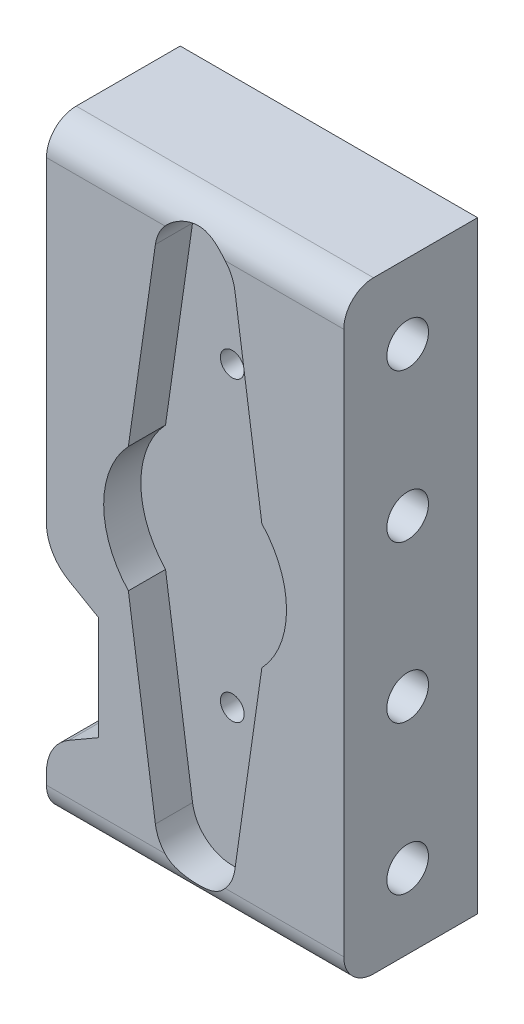
SolidWorks part; units mm, degrees
material "PLA_Holder_Servo"
ref_plane "Front Plane" through (0, 0, 0) normal (0, 0, 1) x (1, 0, 0)
ref_plane "Top Plane" through (0, 0, 0) normal (0, 1, 0) x (1, 0, 0)
ref_plane "Right Plane" through (0, 0, 0) normal (1, 0, 0) x (0, 0, -1)
sketch "Sketch1" plane through (0, 0, 0) normal (0, 0, 1) x (1, 0, 0)
  line L0 (-10, 20.2804) -> (-10, -20.2804)
  line L1 (-10, -20.2804) -> (10, -20.2804)
  line L2 (10, -20.2804) -> (10, 20.2804)
  line L3 (10, 20.2804) -> (-10, 20.2804)
  line L4 (10, -20.2804) -> (-10, 20.2804) construction
  line L5 (10, 20.2804) -> (-10, -20.2804) construction
  point P4 (0, 0)
  dimension "D1" = 20
  dimension "D2" = 40.5608
extrude "Boss-Extrude1" add sketch "Sketch1" against normal blind 9
sketch "Sketch6" plane through (10, 0, 0) normal (1, 0, 0) x (0, 0, -1)
  line L0 (0, -20.2804) -> (0, 20.2804) construction
  line L2 (4.3, 4.95) -> (4.3, 15.6283) construction
  line L3 (0, 0) -> (9, 0) construction
  line L4 (9, -20.2804) -> (9, 20.2804) construction
  line L5 (4.3, -15.2652) -> (4.3, -5.2652) construction
  line L6 (-4.0611, -10.2652) -> (12.6611, -10.2652) construction
  line L7 (9, -20.2804) -> (0, -20.2804) construction
  line L8 (-4.0611, -0.25) -> (12.6611, -0.25) construction
  circle A0 centre (4.3, -15.2652) radius 1.4
  circle A1 centre (4.3, -5.2652) radius 1.4
  circle A2 centre (4.3, 15.2652) radius 1.4
  circle A3 centre (4.3, 5.2652) radius 1.4
  point P18 (4.3, -10.2652)
  point P22 (4.3, -10.2652)
  dimension "D1" = 2.8
  dimension "D2" = 4.7
  dimension "D3" = 10.0152
  dimension "D4" = 10
  dimension "D5" = 10.0152
extrude "Cut-Extrude1" cut sketch "Sketch6" against normal blind 10
sketch "Sketch8" plane through (0, 0, 0) normal (0, 0, 1) x (1, 0, 0)
  line L0 (-10, 20.2804) -> (10, -20.2804) construction
  line L1 (-4.489, -4.2038) -> (-2.6727, -16.8829)
  line L2 (4.3, 4.1125) -> (4.3, -4.1125) construction
  line L3 (0, -16.5) -> (0, 16.5) construction
  line L4 (2.6727, -16.8829) -> (4.489, -4.2038)
  line L5 (-4.3, 4.1125) -> (4.3, 4.1125) construction
  line L6 (-4.3, -4.1125) -> (4.3, -4.1125) construction
  line L7 (4.489, 4.2038) -> (2.6727, 16.8829)
  line L8 (-2.6727, 16.8829) -> (-4.489, 4.2038)
  line L12 (-4.3, -4.1125) -> (-2.4747, -16.8545) construction
  line L13 (2.4747, -16.8545) -> (4.3, -4.1125) construction
  line L14 (4.3, 4.1125) -> (2.4747, 16.8545) construction
  line L15 (-2.4747, 16.8545) -> (-4.3, 4.1125) construction
  arc A0 (-2.6727, -16.8829) -> (2.6727, -16.8829) centre (0, -16.5) ccw
  arc A1 (4.489, -4.2038) -> (4.489, 4.2038) centre (0, 0) ccw
  arc A2 (2.6727, 16.8829) -> (-2.6727, 16.8829) centre (0, 16.5) ccw
  arc A3 (-4.489, 4.2038) -> (-4.489, -4.2038) centre (0, 0) ccw
  arc A12 (-4.3, 4.1125) -> (-4.3, -4.1125) centre (0, 0) ccw construction
  arc A13 (-2.4747, -16.8545) -> (2.4747, -16.8545) centre (0, -16.5) ccw construction
  arc A14 (4.3, -4.1125) -> (4.3, 4.1125) centre (0, 0) ccw construction
  arc A15 (2.4747, 16.8545) -> (-2.4747, 16.8545) centre (0, 16.5) ccw construction
  point P10 (0, 0)
  dimension "D1" = 5.95
  dimension "D3" = 2.5
  dimension "D2" = 8.6
  dimension "D4" = 33
  dimension "D5" = 8.225
  dimension "D6" = 0.2
extrude "Cut-Extrude2" cut sketch "Sketch8" against normal blind 2.5
fillet "Fillet1" radius 2 2 edges at (0, -20.2804, 0) (0, 20.2804, 0) tangent propagation no
sketch "Sketch9" plane through (0, 0, -2.5) normal (0, 0, 1) x (1, 0, 0)
  line L0 (0, 20) -> (0, -49980) construction
  line L1 (-6.15, 0) -> (6.15, 0) construction
  circle A0 centre (0, 10) radius 0.8
  arc A2 (-4.489, 4.2038) -> (-4.489, -4.2038) centre (0, 0) ccw construction
  arc A3 (4.489, -4.2038) -> (4.489, 4.2038) centre (0, 0) ccw construction
  circle A4 centre (0, -10) radius 0.8
  dimension "D1" = 1.6
  dimension "D2" = 10
extrude "Cut-Extrude3" cut sketch "Sketch9" against normal up to surface (6.5 mm away) up to face at (0, 0, -9)
sketch "Sketch10" plane through (-10, 0, 0) normal (-1, 0, 0) x (0, 0, 1)
  line L0 (0, -10.2652) -> (-9, -10.2652) construction
  line L1 (0, 18.2804) -> (0, -18.2804) construction
  line L2 (-9, 20.2804) -> (-9, -20.2804) construction
  line L3 (-9, -20.2804) -> (-2, -20.2804) construction
  line L4 (0, -6.7652) -> (-9, -6.7652)
  line L5 (0, -13.7652) -> (-9, -13.7652)
  line L6 (0, -13.7652) -> (0, -6.7652)
  line L7 (-9, -6.7652) -> (-9, -13.7652)
  dimension "D1" = 10.0152
  dimension "D2" = 3.5
  dimension "D3" = 3.5
extrude "Cut-Extrude4" cut sketch "Sketch10" against normal blind 3.5
chamfer "Chamfer1" distance 3.5 angle 30 2 edges at (-10, -6.7652, -4.5) (-10, -13.7652, -4.5) first distance on face at (-8.25, -6.7652, -4.5) first distance on face at (-8.25, -13.7652, -4.5)
fillet "Fillet2" radius 3 2 edges at (-10, -4.7444, -4.5) (-10, -15.7859, -4.5)
